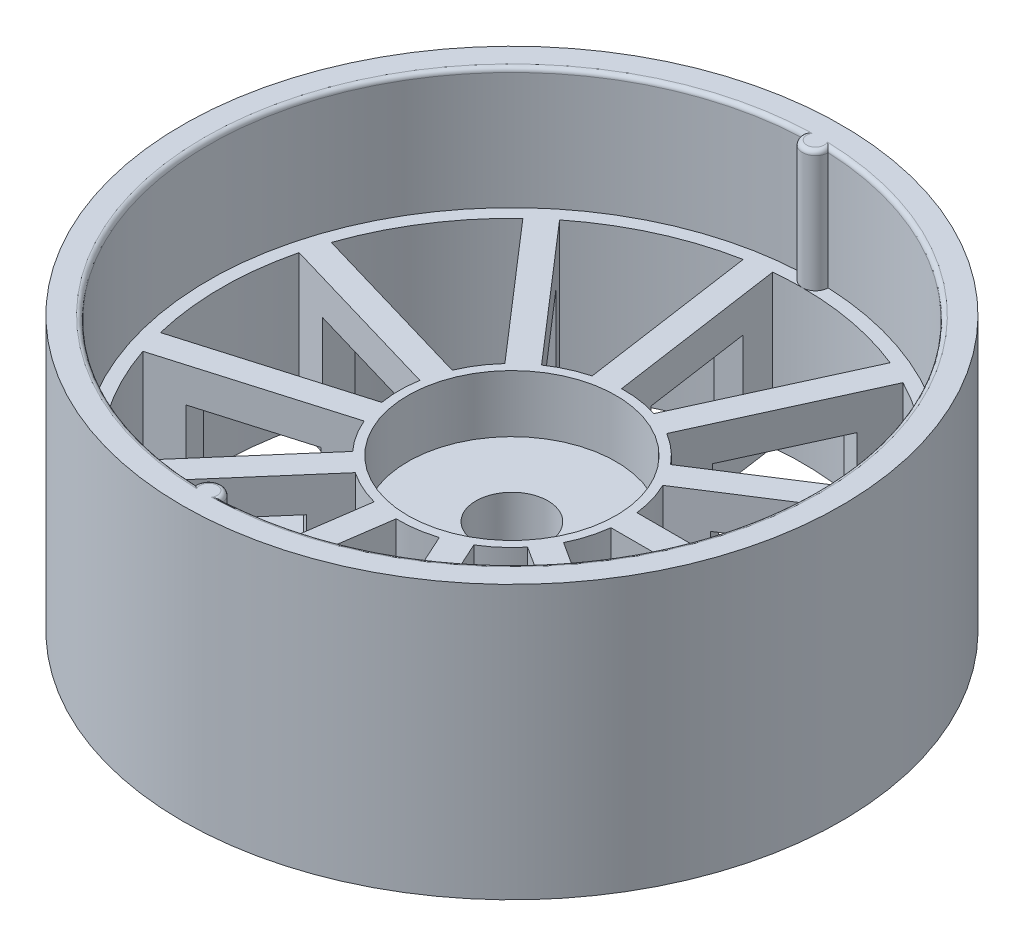
SolidWorks part; units mm, degrees
note: The reader was unsure of these and kept them because the rebuilt part matched: shared geometry of "Sketch1<3>".
ref_plane "Front Plane" through (0, 0, 0) normal (0, 0, 1) x (1, 0, 0)
ref_plane "Top Plane" through (0, 0, 0) normal (0, 1, 0) x (1, 0, 0)
ref_plane "Right Plane" through (0, 0, 0) normal (1, 0, 0) x (0, 0, -1)
sketch "Sketch1" plane through (0, 0, 0) normal (0, 1, 0) x (1, 0, 0)
  line L3 (0, 0) -> (0, 3.226) construction
  line L4 (0, 3.226) -> (2.6106, 3.226)
  line L5 (0, 3.226) -> (-2.6106, 3.226)
  arc A0 (1.4997, -34.9679) -> (34.9678, -1.5001) centre (0, 0) ccw
  circle A1 centre (0, 0) radius 38
  arc A2 (-2.6106, 3.226) -> (2.6106, 3.226) centre (0, 0) ccw
  circle A3 centre (0, 0) radius 35 construction
  arc A7 (-1.4997, 34.9679) -> (1.4997, 34.9679) centre (0, 35) ccw
  arc A8 (34.9678, -1.5001) -> (1.4997, 34.9679) centre (0, 0) ccw
  arc A9 (-1.4997, 34.9679) -> (-35, 0) centre (0, 0) ccw
  arc A10 (-35, 0) -> (-1.5003, -34.9678) centre (0, 0) ccw
  arc A11 (1.4997, -34.9679) -> (-1.5003, -34.9678) centre (-0.0003, -34.9679) ccw
  point P8 (-0.0003, -33.4679)
  dimension "D1" = 3
  dimension "D2" = 1.5
  dimension "D3" = 4.15
  dimension "D4" = 35
  dimension "D5" = 1.5
  dimension "D6" = 1.5
  dimension "D11" = 1.4997
extrude "Boss-Extrude1" add sketch "Sketch1" along normal blind 17.5
extrude "Boss-Extrude2" add sketch "Sketch1<3>" along normal blind 31.5
sketch "Sketch1<3>" plane through (0, 0, 0) normal (0, 1, 0) x (1, 0, 0) same geometry as "Sketch1"
fillet "Fillet2" radius 0.5 4 edges at (35, 31.5, 0) (-35, 31.5, -0.0003) (0, 31.5, -33.5) (-0.0003, 31.5, 33.4679)
chamfer "Chamfer1" distance 1 angle 45 2 edges at (0, 0, -3.226) (0, 0, 4.15)
sketch "Sketch2" plane through (0, 0, 0) normal (0, -1, 0) x (1, 0, 0)
  line L1 (-3.7528, 6.5) -> (-7.5056, 0)
  line L2 (-7.5056, 0) -> (-3.7528, -6.5)
  line L3 (-3.7528, -6.5) -> (3.7528, -6.5)
  line L4 (3.7528, -6.5) -> (7.5056, 0)
  line L5 (7.5056, 0) -> (3.7528, 6.5)
  line L6 (3.7528, 6.5) -> (-3.7528, 6.5)
  circle A0 centre (0, 0) radius 6.5 construction
  dimension "D2" = 13
extrude "Cut-Extrude1" cut sketch "Sketch2" against normal blind 5.6
sketch "Sketch3" plane through (0, 17.5, 0) normal (0, 1, 0) x (1, 0, 0)
  circle A0 centre (0, 0) radius 12
  dimension "D1" = 24
extrude "Cut-Extrude2" cut sketch "Sketch3" against normal blind 6.6
sketch "Sketch4" plane through (0, 17.5, 0) normal (0, 1, 0) x (1, 0, 0)
  circle A0 centre (0, 0) radius 4.15
  dimension "D1" = 8.3
extrude "Cut-Extrude3" cut sketch "Sketch4" against normal through all
sketch "Sketch5" plane through (0, 17.5, 0) normal (0, 1, 0) x (1, 0, 0)
  line L10 (13, 0) -> (33.5, 0) construction
  line L11 (12.9132, -1.5) -> (33.4664, -1.5)
  line L12 (12.9132, 1.5) -> (33.4664, 1.5)
  line L13 (11.6742, -5.7195) -> (28.9647, -16.8314)
  line L14 (10.9363, -7.0283) -> (28.182, -18.1115) construction
  line L15 (10.0523, -8.2433) -> (27.3428, -19.3552)
  line L16 (6.7288, -11.1231) -> (15.2669, -29.819)
  line L17 (5.4004, -11.8252) -> (13.9164, -30.4727) construction
  line L18 (3.9999, -12.3694) -> (12.538, -31.0652)
  line L19 (-0.353, -12.9952) -> (-3.278, -33.3392)
  line L20 (-1.8501, -12.8677) -> (-4.7675, -33.159) construction
  line L21 (-3.3225, -12.5683) -> (-6.2475, -32.9123)
  line L22 (-7.3227, -10.7414) -> (-20.7822, -26.2745)
  line L23 (-8.5132, -9.8247) -> (-21.9378, -25.3176) construction
  line L24 (-9.59, -8.7768) -> (-23.0495, -24.3099)
  line L25 (-11.9675, -5.0773) -> (-31.6882, -10.8678)
  line L26 (-12.4734, -3.6625) -> (-32.143, -9.438) construction
  line L27 (-12.8127, -2.1988) -> (-32.5334, -7.9893)
  line L28 (-12.8127, 2.1988) -> (-32.5334, 7.9893)
  line L29 (-12.4734, 3.6625) -> (-32.143, 9.438) construction
  line L30 (-11.9675, 5.0773) -> (-31.6882, 10.8678)
  line L31 (-9.59, 8.7768) -> (-23.0495, 24.3099)
  line L32 (-8.5132, 9.8247) -> (-21.9378, 25.3176) construction
  line L33 (-7.3227, 10.7414) -> (-20.7822, 26.2745)
  line L34 (-3.3225, 12.5683) -> (-6.2475, 32.9123)
  line L35 (-1.8501, 12.8677) -> (-4.7675, 33.159) construction
  line L36 (-0.353, 12.9952) -> (-3.278, 33.3392)
  line L37 (3.9999, 12.3694) -> (12.538, 31.0652)
  line L38 (5.4004, 11.8252) -> (13.9164, 30.4727) construction
  line L39 (6.7288, 11.1231) -> (15.2669, 29.819)
  line L40 (10.0523, 8.2433) -> (27.3428, 19.3552)
  line L41 (10.9363, 7.0283) -> (28.182, 18.1115) construction
  line L42 (11.6742, 5.7195) -> (28.9647, 16.8314)
  circle A0 centre (0, 0) radius 33.5
  arc A1 (-1.4997, 34.9679) -> (1.4997, 34.9679) centre (0, 35) ccw construction
  circle A2 centre (0, 0) radius 13
  circle A3 centre (0, 0) radius 12 construction
  dimension "D1" = 1
  dimension "D2" = 3
  dimension "D4" = 11
  dimension "D3" = 1.5
extrude "Cut-Extrude4" cut sketch "Sketch5" against normal through all contours A2 L40 A0 L39 | A2 L12 A0 L42 | A2 L13 A0 L11 | A2 L16 A0 L15 | A2 L19 A0 L25 L18 | A2 L22 A0 L21 | A2 L25 A0 L24 | A2 L28 A0 L27 | A2 L31 A0 L30 | A2 L34 A0 L33 | A2 L37 A0 L36
sketch "Sketch6" plane through (-0.811, 0, -1.2619) normal (-0.5406, 0, -0.8413) x (-0.8413, 0, 0.5406)
  line L0 (-23.1898, 17.5) -> (-23.1898, 13.5) construction
  line L3 (-12.9132, 17.5) -> (-33.4664, 17.5) construction
  line L4 (-23.1898, 0) -> (-23.1898, 4) construction
  line L5 (-12.9132, 0) -> (-33.4664, 0) construction
  line L6 (-33.4664, 8.75) -> (-29.4664, 8.75) construction
  line L7 (-33.4664, 0) -> (-33.4664, 17.5) construction
  line L8 (-12.9132, 8.75) -> (-16.9132, 8.75) construction
  line L9 (-12.9132, 0) -> (-12.9132, 17.5) construction
  line L11 (-29.4664, 13.5) -> (-16.9132, 13.5)
  line L12 (-29.4664, 13.5) -> (-29.4664, 4)
  line L13 (-29.4664, 4) -> (-16.9132, 4)
  line L14 (-16.9132, 13.5) -> (-16.9132, 4)
  point P20 (0, 0)
  point P21 (0, 0)
  dimension "D1" = 4
  dimension "D2" = 4
extrude "Cut-Extrude5" cut sketch "Sketch6" against normal up to next
pattern_circular "CirPattern1" count 11 over 360 about axis through (0, 0, 0) along (0, 1, 0) of "Cut-Extrude5"
